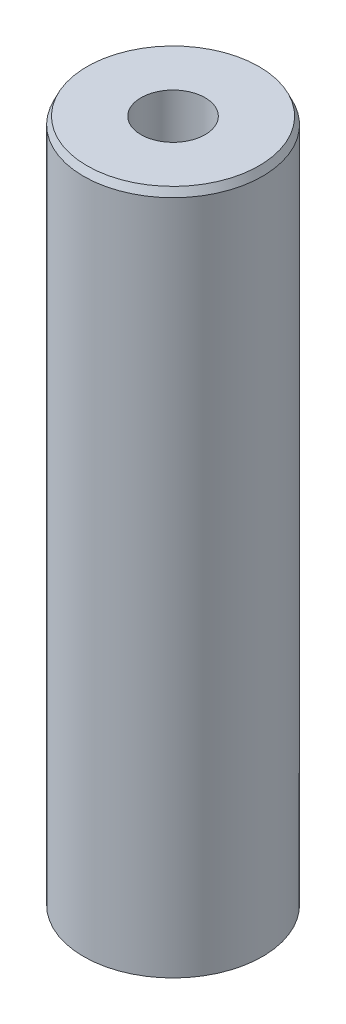
SolidWorks part; units mm, degrees
ref_plane "Front Plane" through (0, 0, 0) normal (0, 0, 1) x (1, 0, 0)
ref_plane "Top Plane" through (0, 0, 0) normal (0, 1, 0) x (1, 0, 0)
ref_plane "Right Plane" through (0, 0, 0) normal (1, 0, 0) x (0, 0, -1)
sketch "Sketch1" plane through (0, 0, 0) normal (0, 1, 0) x (1, 0, 0)
  circle A0 centre (0, 0) radius 57.5
  dimension "SHAFT_OD" = 115
extrude "Boss-Extrude1" add sketch "Sketch1" along normal blind 441.3896
sketch "Sketch2" plane through (0, 0, 0) normal (0, 1, 0) x (1, 0, 0)
  circle A0 centre (0, 0) radius 20.6156
  dimension "BORE_D" = 41.2311
extrude "Cut-Extrude1" cut sketch "Sketch2" along normal through all
chamfer "Chamfer1" distance 4.742 angle 25.014 2 edges at (0, 441.3896, 57.5) (0, 0, 57.5) first distance on face at (0, 441.3896, 57.5) first distance on face at (0, 0, 20.6156)
